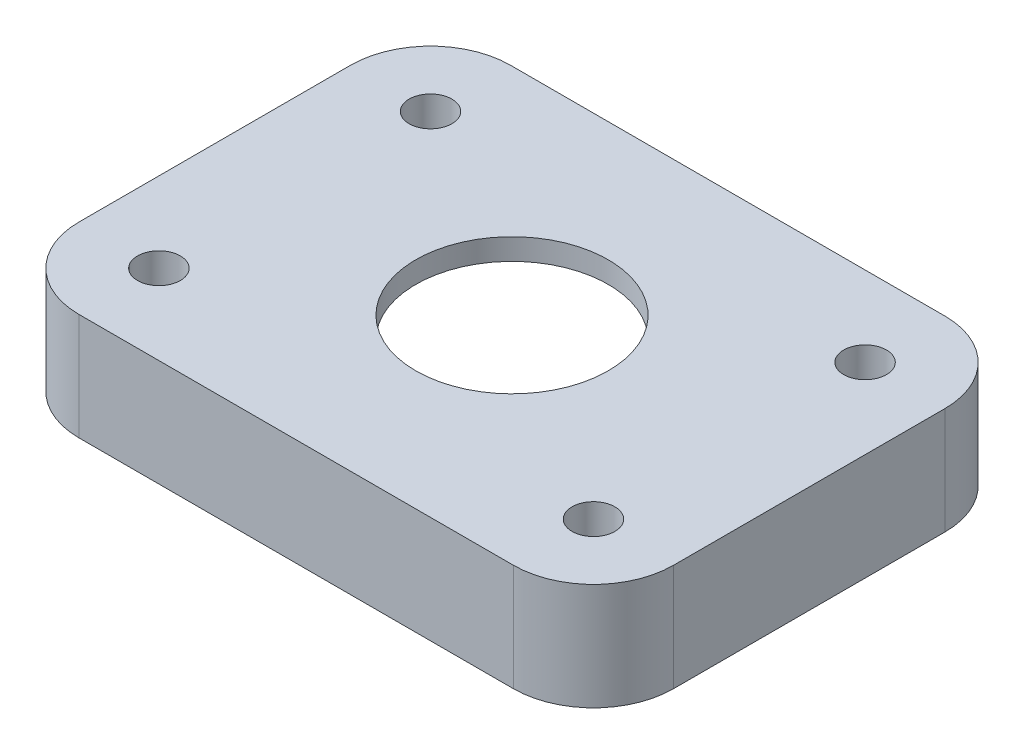
SolidWorks part; units mm, degrees
ref_plane "Front Plane" through (0, 0, 0) normal (0, 0, 1) x (1, 0, 0)
ref_plane "Top Plane" through (0, 0, 0) normal (0, 1, 0) x (1, 0, 0)
ref_plane "Right Plane" through (0, 0, 0) normal (1, 0, 0) x (0, 0, -1)
sketch "Sketch1" plane through (0, 0, 0) normal (0, 1, 0) x (1, 0, 0)
  line L8 (-2.54, 17.78) -> (-22.86, 17.78)
  line L9 (-25.4, 15.24) -> (-25.4, 2.54)
  line L10 (-22.86, 0) -> (-2.54, 0)
  line L11 (0, 2.54) -> (0, 15.24)
  arc A8 (0, 15.24) -> (-2.54, 17.78) centre (-2.54, 15.24) ccw
  arc A9 (-22.86, 17.78) -> (-25.4, 15.24) centre (-22.86, 15.24) ccw
  arc A10 (-25.4, 2.54) -> (-22.86, 0) centre (-22.86, 2.54) ccw
  arc A11 (-2.54, 0) -> (0, 2.54) centre (-2.54, 2.54) ccw
  circle A12 centre (-22.86, 2.54) radius 1.25
  circle A13 centre (-2.54, 2.54) radius 1.25
  circle A14 centre (-2.54, 15.24) radius 1.25
  circle A15 centre (-22.86, 15.24) radius 1.25
sketch "Sketch2" plane through (0, 0, 0) normal (0, 1, 0) x (1, 0, 0)
  line L4 (-26.6, 15.24) -> (-26.6, 2.54)
  line L5 (-22.86, -1.2) -> (-2.54, -1.2)
  line L6 (1.2, 2.54) -> (1.2, 15.24)
  line L7 (-2.54, 18.98) -> (-22.86, 18.98)
  line L9 (0.2, 2.54) -> (0.2, 15.24)
  line L10 (-22.86, -0.2) -> (-2.54, -0.2)
  line L11 (-25.6, 15.24) -> (-25.6, 2.54)
  line L13 (0.2, 2.54) -> (0.2, 15.24)
  line L14 (-22.86, -0.2) -> (-2.54, -0.2)
  line L15 (-25.6, 15.24) -> (-25.6, 2.54)
  line L19 (-2.54, 17.98) -> (-22.86, 17.98)
  line L20 (-2.54, 17.98) -> (-22.86, 17.98) construction
  line L21 (-2.54, 17.98) -> (-22.86, 17.98)
  arc A4 (-22.86, 18.98) -> (-26.6, 15.24) centre (-22.86, 15.24) ccw
  arc A5 (-26.6, 2.54) -> (-22.86, -1.2) centre (-22.86, 2.54) ccw
  arc A6 (-2.54, -1.2) -> (1.2, 2.54) centre (-2.54, 2.54) ccw
  arc A7 (1.2, 15.24) -> (-2.54, 18.98) centre (-2.54, 15.24) ccw
  arc A8 (0.2, 15.24) -> (-2.54, 17.98) centre (-2.54, 15.24) ccw
  arc A9 (-2.54, -0.2) -> (0.2, 2.54) centre (-2.54, 2.54) ccw
  arc A10 (-25.6, 2.54) -> (-22.86, -0.2) centre (-22.86, 2.54) ccw
  arc A11 (-22.86, 17.98) -> (-25.6, 15.24) centre (-22.86, 15.24) ccw
  arc A12 (0.2, 15.24) -> (-2.54, 17.98) centre (-2.54, 15.24) ccw
  arc A13 (-2.54, -0.2) -> (0.2, 2.54) centre (-2.54, 2.54) ccw
  arc A14 (-25.6, 2.54) -> (-22.86, -0.2) centre (-22.86, 2.54) ccw
  arc A15 (-22.86, 17.98) -> (-25.6, 15.24) centre (-22.86, 15.24) ccw
  dimension "D1" = 0.2
  dimension "D2" = 1
extrude "Boss-Extrude1" add sketch "Sketch2" along normal blind 4
sketch "Sketch3" plane through (0, 4, 0) normal (0, 1, 0) x (1, 0, 0)
  line L4 (-26.6, 15.24) -> (-26.6, 2.54)
  line L5 (-22.86, -1.2) -> (-2.54, -1.2)
  line L6 (1.2, 2.54) -> (1.2, 15.24)
  line L7 (-2.54, 18.98) -> (-22.86, 18.98)
  line L8 (-26.6, 15.24) -> (-26.6, 2.54)
  line L9 (-22.86, -1.2) -> (-2.54, -1.2)
  line L10 (1.2, 2.54) -> (1.2, 15.24)
  line L11 (-2.54, 18.98) -> (-22.86, 18.98)
  arc A4 (-22.86, 18.98) -> (-26.6, 15.24) centre (-22.86, 15.24) ccw
  arc A5 (-26.6, 2.54) -> (-22.86, -1.2) centre (-22.86, 2.54) ccw
  arc A6 (-2.54, -1.2) -> (1.2, 2.54) centre (-2.54, 2.54) ccw
  arc A7 (1.2, 15.24) -> (-2.54, 18.98) centre (-2.54, 15.24) ccw
  arc A8 (-22.86, 18.98) -> (-26.6, 15.24) centre (-22.86, 15.24) ccw
  arc A9 (-26.6, 2.54) -> (-22.86, -1.2) centre (-22.86, 2.54) ccw
  arc A10 (-2.54, -1.2) -> (1.2, 2.54) centre (-2.54, 2.54) ccw
  arc A11 (1.2, 15.24) -> (-2.54, 18.98) centre (-2.54, 15.24) ccw
  dimension "D1" = 0
extrude "Boss-Extrude2" add sketch "Sketch3" along normal blind 1
sketch "Sketch4" plane through (0, 0, 0) normal (0, -1, 0) x (1, 0, 0)
  line L0 (-20.86, -2.54) -> (-20.86, 0.2)
  line L1 (-22.86, 0.2) -> (-2.54, 0.2) construction
  line L2 (-22.86, -4.54) -> (-25.6, -4.54)
  line L3 (-25.6, -15.24) -> (-25.6, -2.54) construction
  circle A0 centre (-22.86, -2.54) radius 2
  circle A1 centre (-2.54, -2.54) radius 1.8945
  circle A2 centre (-22.86, -2.54) radius 1.25 construction
  circle A3 centre (-22.86, -2.54) radius 1.25
  line M14 (-25.6, -15.24) -> (-25.6, -2.54)
  arc M15 (-25.6, -2.54) -> (-22.86, 0.2) centre (-22.86, -2.54) cw
  line M16 (-22.86, 0.2) -> (-2.54, 0.2)
  dimension "D1" = 4
extrude "Boss-Extrude3" add sketch "Sketch4" along normal blind 3.2 from surface contours A0 L0 L2 M16 M15 M14 | A0 A3 region at (-24.3216, 0, -1.0784) region at (-21.4858, 0, -3.9142) starting at face at (-12.7, 4, -8.89)
ref_plane "Plane1" through (0, 0, -8.89) normal (0, 0, -1) x (-1, 0, 0)
ref_plane "Plane2" through (-12.7, 0, 0) normal (-1, 0, 0) x (0, 0, 1)
mirror "Mirror3" about plane through (-12.7, 0, 0) normal (-1, 0, 0) of "Boss-Extrude3"
mirror "Mirror4" about plane through (0, 0, -8.89) normal (0, 0, -1) of "Mirror3"
sketch "Sketch5" plane through (0, 5, 0) normal (0, 1, 0) x (1, 0, 0)
  line L0 (-2.54, 18.98) -> (-22.86, 18.98) construction
  line L1 (1.2, 2.54) -> (1.2, 15.24) construction
  circle A0 centre (-12.7, 8.89) radius 4.5
  point P4 (-12.7, 18.98)
  point P7 (1.2, 8.89)
  dimension "D1" = 9
extrude "Cut-Extrude1" cut sketch "Sketch5" against normal blind 3
extrude "Cut-Extrude2" cut sketch "Sketch1" along normal blind 10 contours A12 | A15 | A14 | A13
fillet "Fillet2" radius 1 8 edges at (-25.6, 2.4, -13.24) (-20.86, 2.4, 0.2) (-4.54, 2.4, 0.2) (0.2, 2.4, -4.54) (0.2, 2.4, -13.24) (-4.54, 2.4, -17.98) (-20.86, 2.4, -17.98) (-25.6, 2.4, -4.54)
sketch "Sketch6" plane through (0, 5, 0) normal (0, 1, 0) x (1, 0, 0)
  circle A1 centre (-2.54, 15.24) radius 1
  circle A3 centre (-22.86, 15.24) radius 1
  circle A4 centre (-2.54, 2.54) radius 1
  circle A5 centre (-22.86, 2.54) radius 1
  point P5 (-22.86, 15.24)
  dimension "D1" = 2
extrude "Extrude-Thin1" add sketch "Sketch6" against normal up to surface (4.2 mm away) thin up to face at (-22.86, 0.8, -13.99) thin type one direction wall 1
